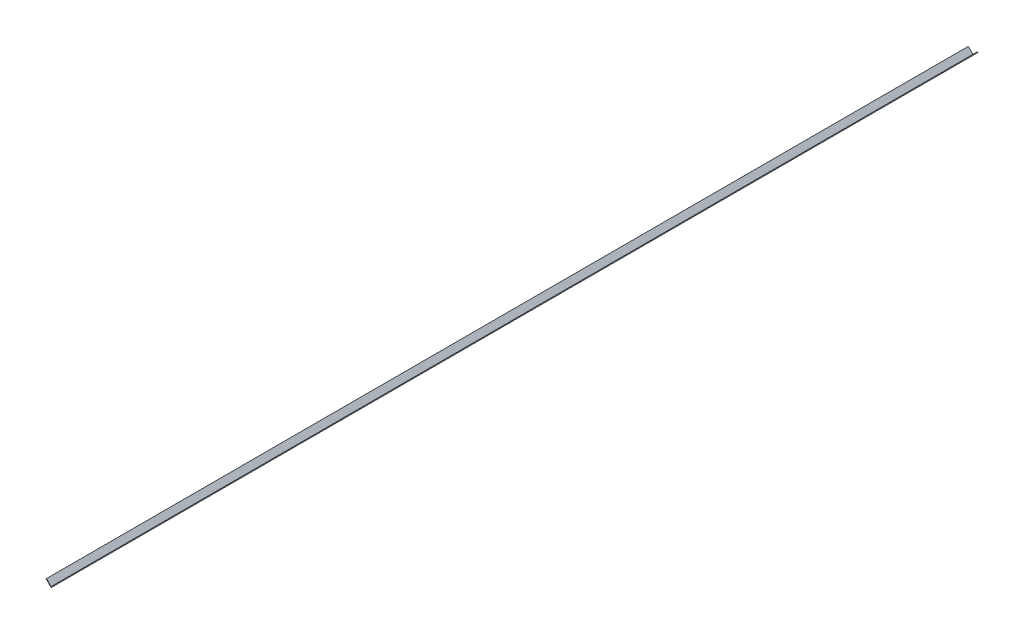
SolidWorks part; units mm, degrees
material "6061 Alloy"
ref_plane "Front Plane" through (0, 0, 0) normal (0, 0, 1) x (1, 0, 0)
ref_plane "Top Plane" through (0, 0, 0) normal (0, 1, 0) x (1, 0, 0)
ref_plane "Right Plane" through (0, 0, 0) normal (1, 0, 0) x (0, 0, -1)
sketch "Sketch1" plane through (0, 0, 0) normal (0, 0, 1) x (1, 0, 0)
  line L0 (0, 0) -> (-8.9803, 8.9803)
  line L1 (-8.9803, 8.9803) -> (-9.8783, 8.0822)
  line L2 (-9.8783, 8.0822) -> (0, -1.7961)
  line L3 (0, -1.7961) -> (9.8783, 8.0822)
  line L4 (9.8783, 8.0822) -> (8.9803, 8.9803)
  line L5 (8.9803, 8.9803) -> (0, 0)
  line L6 (-13.872, 0) -> (16.6117, 0) construction
  dimension "D1" = 1.27
  dimension "D2" = 12.7
extrude "Boss-Extrude1" add sketch "Sketch1" along normal blind 1714.5 and the other way blind 76.2
